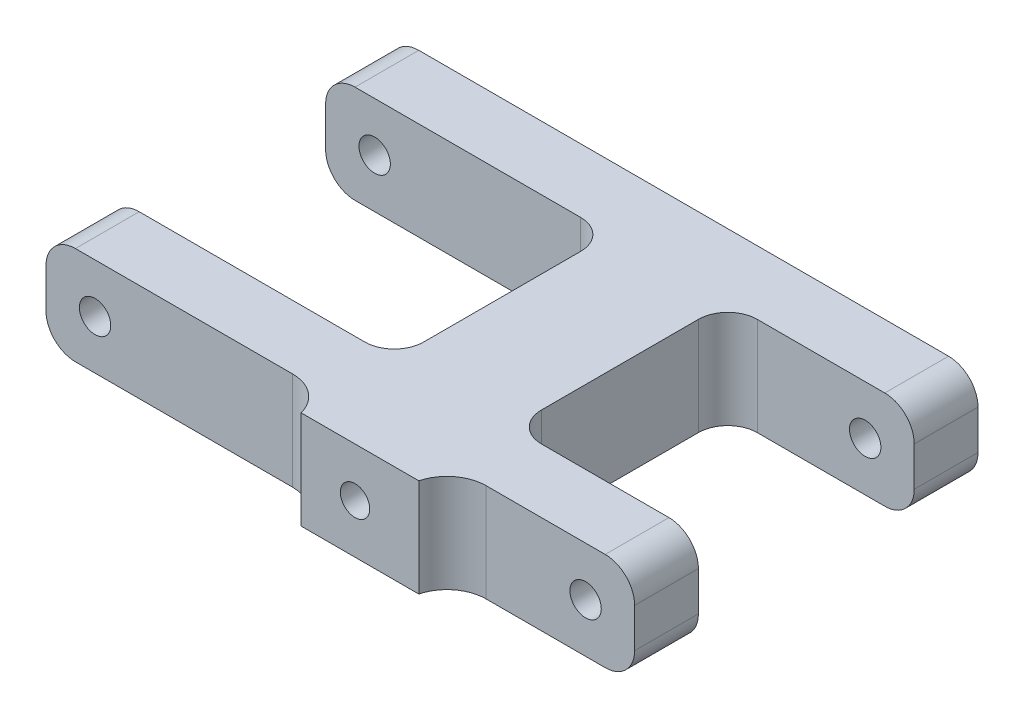
SolidWorks part; units mm, degrees
ref_plane "Front" through (0, 0, 0) normal (0, 0, 1) x (1, 0, 0)
ref_plane "Top" through (0, 0, 0) normal (0, 1, 0) x (1, 0, 0)
ref_plane "Right" through (0, 0, 0) normal (1, 0, 0) x (0, 0, -1)
sketch "Sketch1" plane through (0, 0, 0) normal (0, 1, 0) x (1, 0, 0)
  line L1 (0, 0) -> (60, 0)
  line L2 (0, 0) -> (0, -35)
  line L3 (0, -35) -> (60, -35)
  line L4 (60, 0) -> (60, -35)
  dimension "D1" = 35
  dimension "D2" = 60
extrude "Boss-Extrude1" add sketch "Sketch1" along normal blind 10
sketch "Sketch2" plane through (60, 0, 0) normal (1, 0, 0) x (0, 0, -1)
  line L0 (-35, 10) -> (0, 10) construction
  line L1 (-28.5, 10) -> (-6.5, 10)
  line L2 (-28.5, 10) -> (-28.5, 0)
  line L3 (-28.5, 0) -> (-6.5, 0)
  line L4 (-6.5, 10) -> (-6.5, 0)
  line L5 (-35, 0) -> (0, 0) construction
  line L6 (-35, 10) -> (-35, 0) construction
  line L7 (0, 10) -> (0, 0) construction
  dimension "D1" = 6.5
  dimension "D2" = 6.5
extrude "Cut-Extrude1" cut sketch "Sketch2" against normal blind 19
sketch "Sketch3" plane through (0, 0, 0) normal (-1, 0, 0) x (0, 0, 1)
  line L0 (0, 10) -> (35, 10) construction
  line L1 (6.5, 10) -> (28.5, 10)
  line L2 (6.5, 10) -> (6.5, 0)
  line L3 (6.5, 0) -> (28.5, 0)
  line L4 (28.5, 10) -> (28.5, 0)
  line L5 (0, 0) -> (35, 0) construction
  line L6 (35, 10) -> (35, 0) construction
  line L7 (0, 10) -> (0, 0) construction
  dimension "D1" = 6.5
  dimension "D2" = 6.5
extrude "Cut-Extrude2" cut sketch "Sketch3" against normal blind 29
sketch "Sketch5" plane through (0, 0, 35) normal (0, 0, 1) x (1, 0, 0)
  line L0 (0, 10) -> (60, 10) construction
  line L1 (0, 10) -> (0, 0) construction
  circle A0 centre (5, 5) radius 1.6
  circle A1 centre (55, 5) radius 1.6
  dimension "D1" = 3.2
  dimension "D2" = 5
  dimension "D3" = 5
  dimension "D4" = 2
extrude "Cut-Extrude4" cut sketch "Sketch5" against normal through all
fillet "Fillet1" radius 3 8 edges at (0, 0, 31.75) (0, 10, 31.75) (0, 0, 3.25) (0, 10, 3.25) (60, 10, 3.25) (60, 0, 3.25) (60, 0, 31.75) (60, 10, 31.75)
fillet "Fillet2" radius 3 4 edges at (41, 5, 28.5) (41, 5, 6.5) (29, 5, 28.5) (29, 5, 6.5)
sketch "Sketch7" plane through (0, 0, 35) normal (0, 0, 1) x (1, 0, 0)
  line L0 (3, 10) -> (57, 10) construction
  line L1 (29, 10) -> (41, 10)
  line L2 (29, 10) -> (29, 0)
  line L3 (29, 0) -> (41, 0)
  line L4 (41, 10) -> (41, 0)
  line L5 (3, 0) -> (57, 0) construction
  line L6 (60, 7) -> (60, 3) construction
  line L7 (0, 7) -> (0, 3) construction
  dimension "D1" = 19
  dimension "D2" = 29
extrude "Boss-Extrude2" add sketch "Sketch7" along normal blind 3
sketch "Sketch6" plane through (0, 0, 35) normal (0, 0, 1) x (1, 0, 0)
  line L0 (3, 0) -> (29, 0) construction
  line L2 (0, 7) -> (0, 3) construction
  circle A0 centre (34.5, 5) radius 1.5
  dimension "D1" = 3
  dimension "D2" = 5
  dimension "D3" = 34.5
extrude "Cut-Extrude5" cut sketch "Sketch6" against normal blind 15 and the other way blind 3
fillet "Fillet3" radius 4 2 edges at (41, 5, 35) (29, 5, 35)
